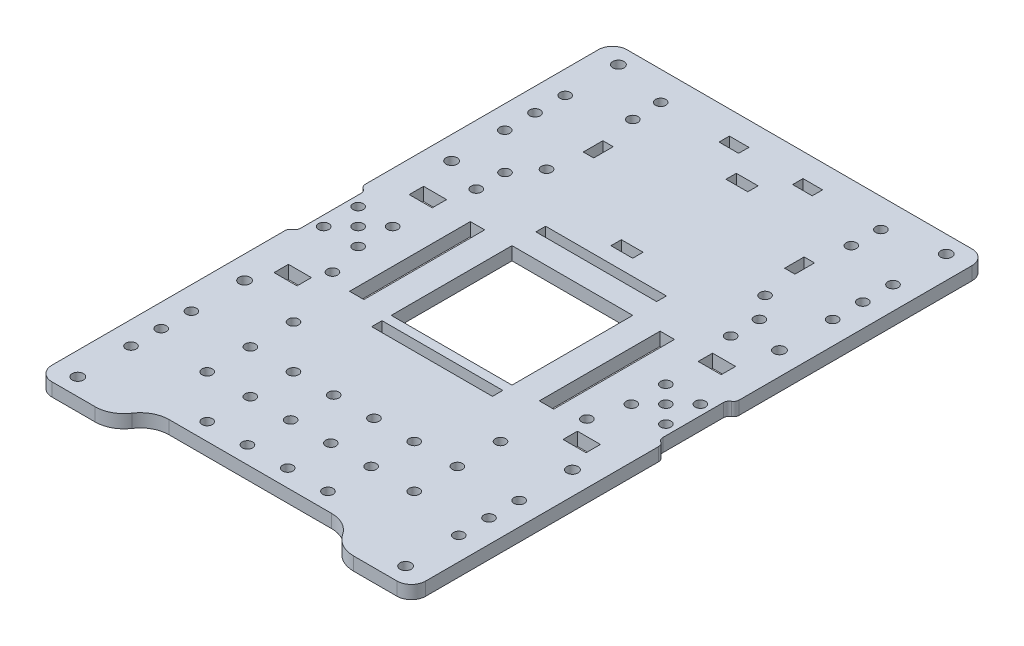
SolidWorks part; units mm, degrees
ref_plane "前视基准面" through (0, 0, 0) normal (0, 0, 1) x (1, 0, 0)
ref_plane "上视基准面" through (0, 0, 0) normal (0, 1, 0) x (1, 0, 0)
ref_plane "右视基准面" through (0, 0, 0) normal (1, 0, 0) x (0, 0, -1)
other "Configuration Table"
sketch "草图2" plane through (0, 0, 0) normal (0, 1, 0) x (1, 0, 0)
  line L0 (-65, 0) -> (65, 0) construction
  line L1 (-65, 100) -> (65, 100)
  line L2 (-65, 100) -> (-65, -100)
  line L3 (-65, -100) -> (65, -100)
  line L4 (65, 100) -> (65, -100)
  line L5 (-65, 100) -> (65, -100) construction
  line L6 (-65, -100) -> (65, 100) construction
  line L7 (65, 0) -> (63, 0) construction
  line L8 (63, 0) -> (59.5, 0) construction
  line L9 (59.5, 0) -> (47.5, 0) construction
  line L10 (47.5, 0) -> (53.5, 0) construction
  line L11 (53.5, 0) -> (53.5, 6) construction
  line L12 (53.5, 6) -> (53.5, -6) construction
  line L13 (53.5, -6) -> (47.5, -6) construction
  line L14 (47.5, -6) -> (47.5, 6) construction
  line L15 (47.5, 6) -> (59.5, 6) construction
  line L16 (59.5, 6) -> (59.5, -6) construction
  line L17 (-65, 0) -> (-63, 0) construction
  line L18 (-63, 0) -> (-59.5, 0) construction
  line L19 (-59.5, 0) -> (-47.5, 0) construction
  line L20 (-47.5, 0) -> (-53.5, 0) construction
  line L21 (-53.5, 0) -> (-53.5, 6) construction
  line L22 (-53.5, 6) -> (-53.5, -6) construction
  line L23 (-53.5, -6) -> (-59.5, -6) construction
  line L24 (-59.5, -6) -> (-59.5, 6) construction
  line L25 (-59.5, 6) -> (-47.5, 6) construction
  line L26 (-47.5, 6) -> (-47.5, -6) construction
  circle A0 centre (-59.5, 6) radius 1.8
  circle A1 centre (-47.5, 6) radius 1.8
  circle A2 centre (-59.5, -6) radius 1.8
  circle A3 centre (-47.5, -6) radius 1.8
  circle A4 centre (-53.5, 0) radius 1.8
  circle A5 centre (53.5, 0) radius 1.8
  circle A6 centre (59.5, 6) radius 1.8
  circle A7 centre (59.5, -6) radius 1.8
  circle A8 centre (47.5, -6) radius 1.8
  circle A9 centre (47.5, 6) radius 1.8
  point P0 (0, 0)
  dimension "D13" = 3.6
  dimension "D14" = 3.6
  dimension "D15" = 3.6
  dimension "D16" = 3.6
  dimension "D17" = 3.6
  dimension "D18" = 3.6
  dimension "D19" = 3.6
  dimension "D20" = 3.6
  dimension "D21" = 3.6
  dimension "D22" = 3.6
  dimension "D1" = 200
  dimension "D2" = 130
  dimension "D3" = 2
  dimension "D4" = 3.5
  dimension "D5" = 12
  dimension "D6" = 6
  dimension "D7" = 12
  dimension "D8" = 2
  dimension "D9" = 3.5
  dimension "D10" = 12
  dimension "D11" = 6
  dimension "D12" = 12
extrude "凸台-拉伸1" add sketch "草图2" along normal blind 4.6
fillet "圆角1" radius 5 4 edges at (-65, 2.3, -100) (65, 2.3, -100) (-65, 2.3, 100) (65, 2.3, 100)
sketch "草图3" plane through (0, 4.6, 0) normal (0, 1, 0) x (1, 0, 0)
  line L0 (-65, 0) -> (65, 0) construction
  line L1 (-65, 95) -> (-65, -95) construction
  line L2 (65, -95) -> (65, 95) construction
  line L4 (-63, 12) -> (-67, 12)
  line L5 (-63, 12) -> (-63, -12)
  line L6 (-63, -12) -> (-67, -12)
  line L7 (-67, 12) -> (-67, -12)
  line L8 (-63, 12) -> (-67, -12) construction
  line L9 (-63, -12) -> (-67, 12) construction
  line L10 (63, 12) -> (67, 12)
  line L11 (63, 12) -> (63, -12)
  line L12 (63, -12) -> (67, -12)
  line L13 (67, 12) -> (67, -12)
  line L14 (63, 12) -> (67, -12) construction
  line L15 (63, -12) -> (67, 12) construction
  dimension "D1" = 24
  dimension "D2" = 4
  dimension "D3" = 24
  dimension "D4" = 4
extrude "切除-拉伸1" cut sketch "草图3" against normal blind 4.6
fillet "圆角2" radius 2 4 edges at (65, 2.3, 12) (65, 2.3, -12) (-65, 2.3, 12) (-65, 2.3, -12)
fillet "圆角3" radius 2 4 edges at (-63, 2.3, 12) (-63, 2.3, -12) (63, 2.3, 12) (63, 2.3, -12)
sketch "草图4" plane through (0, 0, 0) normal (0, 1, 0) x (1, 0, 0)
  line L0 (65, 14) -> (57, 14) construction
  line L1 (57, 14) -> (57, 120) construction
  line L2 (65, -14) -> (57, -14) construction
  line L3 (65, -95) -> (65, -14) construction
  line L4 (57, -14) -> (57, -94) construction
  line L5 (57, -94) -> (57, -65) construction
  line L6 (57, -65) -> (57, -54) construction
  line L7 (-65, -94) -> (-57, -94) construction
  line L8 (-65, -14) -> (-65, -95) construction
  line L9 (-57, -94) -> (-57, -65) construction
  line L10 (-57, -65) -> (-57, -54.5) construction
  line L11 (-57, -54.5) -> (-57, -65) construction
  line L12 (-57, -65) -> (-57, -36) construction
  line L13 (57, -65) -> (57, -36) construction
  line L14 (57, 14) -> (57, 36) construction
  line L15 (57, 36) -> (57, 65) construction
  line L16 (57, 65) -> (57, 75.5) construction
  line L17 (57, 75.5) -> (57, 54.5) construction
  line L18 (57, 65) -> (57, 94) construction
  line L19 (-65, 14) -> (-57, 14) construction
  line L20 (-57, 14) -> (-57, 36) construction
  line L21 (-57, 36) -> (-57, 54.5) construction
  line L22 (-57, 54.5) -> (-57, 65) construction
  line L23 (-57, 65) -> (-57, 75.5) construction
  line L24 (-57, 75.5) -> (-57, 94) construction
  line L25 (-57, -65) -> (-57, -75.5) construction
  line L26 (-57, -75.5) -> (57, -75.5) construction
  line L27 (57, -65) -> (57, -54.5) construction
  arc A0 (65, -14) -> (64, -12.2679) centre (63, -14) ccw construction
  circle A1 centre (57, 65) radius 1.8
  circle A2 centre (57, 75.5) radius 1.8
  circle A3 centre (57, 54.5) radius 1.8
  circle A4 centre (57, 94) radius 1.95
  circle A5 centre (57, 36) radius 1.95
  circle A6 centre (-57, 94) radius 1.95
  circle A7 centre (-57, 75.5) radius 1.8
  circle A8 centre (-57, 65) radius 1.8
  circle A9 centre (-57, 54.5) radius 1.8
  circle A10 centre (-57, 36) radius 1.95
  circle A11 centre (-57, -36) radius 1.95
  circle A12 centre (-57, -65) radius 1.8
  circle A13 centre (-57, -54.5) radius 1.8
  circle A14 centre (-57, -75.5) radius 1.8
  circle A15 centre (-57, -94) radius 1.95
  circle A16 centre (57, -65) radius 1.8
  circle A18 centre (57, -75.5) radius 1.8
  circle A19 centre (57, -54.5) radius 1.8
  circle A20 centre (57, -36) radius 1.95
  circle A21 centre (57, -94) radius 1.95
  dimension "D15" = 3.6
  dimension "D16" = 3.6
  dimension "D17" = 3.6
  dimension "D18" = 3.9
  dimension "D19" = 3.9
  dimension "D20" = 3.9
  dimension "D21" = 3.6
  dimension "D22" = 3.6
  dimension "D23" = 3.6
  dimension "D24" = 3.9
  dimension "D25" = 3.9
  dimension "D26" = 3.6
  dimension "D27" = 3.6
  dimension "D29" = 3.6
  dimension "D30" = 3.9
  dimension "D31" = 3.6
  dimension "D32" = 10.5
  dimension "D33" = 3.6
  dimension "D34" = 3.6
  dimension "D35" = 3.9
  dimension "D36" = 3.9
  dimension "D1" = 8
  dimension "D2" = 106
  dimension "D3" = 8
  dimension "D4" = 80
  dimension "D5" = 29
  dimension "D6" = 11
  dimension "D7" = 8
  dimension "D8" = 29
  dimension "D9" = 22
  dimension "D10" = 29
  dimension "D11" = 10.5
  dimension "D12" = 21
  dimension "D13" = 29
  dimension "D14" = 8
  dimension "D28" = 10.5
extrude "切除-拉伸2" cut sketch "草图4" along normal blind 4.6
sketch "草图5" plane through (0, 4.6, 0) normal (0, 1, 0) x (1, 0, 0)
  line L0 (0, 100) -> (38.3, 100) construction
  line L1 (60, 100) -> (-60, 100) construction
  line L2 (38.3, 100) -> (-38.3, 100) construction
  line L3 (-38.3, 100) -> (-38.3, 90) construction
  line L4 (-38.3, 90) -> (-12.8, 90) construction
  line L5 (38.3, 100) -> (38.3, 90) construction
  line L6 (38.3, 90) -> (12.8, 90) construction
  line L7 (0, 21) -> (0, 31) construction
  line L8 (-16.2, 91.8) -> (-9.4, 91.8)
  line L9 (-16.2, 91.8) -> (-16.2, 88.2)
  line L10 (-16.2, 88.2) -> (-9.4, 88.2)
  line L11 (-9.4, 91.8) -> (-9.4, 88.2)
  line L12 (-16.2, 91.8) -> (-9.4, 88.2) construction
  line L13 (-16.2, 88.2) -> (-9.4, 91.8) construction
  line L14 (9.4, 91.8) -> (16.2, 91.8)
  line L15 (9.4, 91.8) -> (9.4, 88.2)
  line L16 (9.4, 88.2) -> (16.2, 88.2)
  line L17 (16.2, 91.8) -> (16.2, 88.2)
  line L18 (9.4, 91.8) -> (16.2, 88.2) construction
  line L19 (9.4, 88.2) -> (16.2, 91.8) construction
  line L20 (-21, 21) -> (21, 21)
  line L21 (-21, 21) -> (-21, -21)
  line L22 (-21, -21) -> (21, -21)
  line L23 (21, 21) -> (21, -21)
  line L24 (-21, 21) -> (21, -21) construction
  line L25 (-21, -21) -> (21, 21) construction
  line L26 (0, 31) -> (0, -21) construction
  line L27 (0, -21) -> (0, -31) construction
  line L28 (-60, -100) -> (60, -100) construction
  line L29 (-21, 32.7) -> (21, 32.7)
  line L30 (-21, 32.7) -> (-21, 29.3)
  line L31 (-21, 29.3) -> (21, 29.3)
  line L32 (21, 32.7) -> (21, 29.3)
  line L33 (-21, 32.7) -> (21, 29.3) construction
  line L34 (-21, 29.3) -> (21, 32.7) construction
  line L35 (-21, -29.3) -> (21, -29.3)
  line L36 (-21, -29.3) -> (-21, -32.7)
  line L37 (-21, -32.7) -> (21, -32.7)
  line L38 (21, -29.3) -> (21, -32.7)
  line L39 (-21, -29.3) -> (21, -32.7) construction
  line L40 (-21, -32.7) -> (21, -29.3) construction
  line L41 (-35, -91) -> (35, -91)
  line L42 (-35, -91) -> (-35, -109)
  line L43 (-35, -109) -> (35, -109)
  line L44 (35, -91) -> (35, -109)
  line L45 (-35, -91) -> (35, -109) construction
  line L46 (-35, -109) -> (35, -91) construction
  circle A0 centre (38.3, 90) radius 1.8
  circle A1 centre (-38.3, 90) radius 1.8
  point P19 (0, 0)
  point P37 (0, -100)
  dimension "D7" = 3.6
  dimension "D8" = 3.6
  dimension "D1" = 38.3
  dimension "D2" = 76.6
  dimension "D3" = 10
  dimension "D4" = 25.5
  dimension "D5" = 10
  dimension "D6" = 25.5
  dimension "D9" = 3.6
  dimension "D10" = 6.8
  dimension "D11" = 3.6
  dimension "D12" = 6.8
  dimension "D13" = 42
  dimension "D14" = 10
  dimension "D15" = 10
  dimension "D16" = 3.4
  dimension "D17" = 42
  dimension "D18" = 3.4
  dimension "D19" = 42
  dimension "D20" = 18
  dimension "D21" = 70
extrude "切除-拉伸3" cut sketch "草图5" against normal blind 4.6
fillet "圆角4" radius 10 2 edges at (-35, 2.3, 100) (35, 2.3, 100)
fillet "圆角5" radius 10 2 edges at (-35, 2.3, 91) (35, 2.3, 91)
sketch "草图6" plane through (0, 4.6, 0) normal (0, 1, 0) x (1, 0, 0)
  line L0 (0, -91) -> (0, -85) construction
  line L1 (28.2466, -91) -> (-28.2466, -91) construction
  line L2 (0, -85) -> (-7, -85) construction
  line L3 (-7, -85) -> (7, -85) construction
  line L4 (7, -85) -> (21, -85) construction
  line L5 (21, -85) -> (21, -70) construction
  line L6 (21, -70) -> (21, -55) construction
  line L7 (21, -55) -> (7, -55) construction
  line L8 (7, -55) -> (-7, -55) construction
  line L9 (-7, -55) -> (-21, -55) construction
  line L10 (-21, -55) -> (-35, -55) construction
  line L11 (-35, -55) -> (-35, -70) construction
  line L12 (-35, -70) -> (-35, -85) construction
  line L13 (-35, -85) -> (-21, -85) construction
  line L14 (21, -85) -> (35, -85) construction
  line L15 (35, -85) -> (35, -70) construction
  line L16 (35, -70) -> (35, -55) construction
  line L17 (35, -55) -> (35, -40) construction
  line L18 (35, -40) -> (21, -40) construction
  line L19 (21, -40) -> (7, -40) construction
  line L20 (7, -40) -> (-7, -40) construction
  line L21 (-7, -40) -> (-21, -40) construction
  line L22 (-21, -40) -> (-35, -40) construction
  line L23 (-35, -40) -> (-35, -70) construction
  line L24 (-35, -70) -> (-21, -70) construction
  line L25 (-21, -70) -> (-7, -70) construction
  line L26 (-7, -70) -> (7, -70) construction
  line L27 (21, -70) -> (36, -70) construction
  line L28 (36, -70) -> (36, -55) construction
  line L29 (36, -55) -> (36, -40) construction
  line L30 (-21, -70) -> (-36, -70) construction
  line L31 (-36, -70) -> (-36, -55) construction
  line L32 (-36, -55) -> (-36, -40) construction
  circle A0 centre (-7, -85) radius 1.8
  circle A1 centre (-21, -85) radius 1.8
  circle A2 centre (7, -85) radius 1.8
  circle A3 centre (21, -85) radius 1.8
  circle A4 centre (21, -70) radius 1.8
  circle A5 centre (7, -70) radius 1.8
  circle A6 centre (-7, -70) radius 1.8
  circle A7 centre (-21, -70) radius 1.8
  circle A8 centre (-21, -55) radius 1.8
  circle A9 centre (-7, -55) radius 1.8
  circle A10 centre (7, -55) radius 1.8
  circle A11 centre (21, -55) radius 1.8
  circle A12 centre (36, -70) radius 1.8
  circle A13 centre (36, -55) radius 1.8
  circle A14 centre (36, -40) radius 1.8
  circle A15 centre (-36, -40) radius 1.8
  circle A16 centre (-36, -55) radius 1.8
  circle A17 centre (-36, -70) radius 1.8
  dimension "D15" = 3.6
  dimension "D16" = 3.6
  dimension "D17" = 3.6
  dimension "D18" = 3.6
  dimension "D19" = 3.6
  dimension "D20" = 3.6
  dimension "D21" = 3.6
  dimension "D22" = 3.6
  dimension "D23" = 3.6
  dimension "D24" = 3.6
  dimension "D25" = 3.6
  dimension "D26" = 3.6
  dimension "D27" = 15
  dimension "D33" = 3.6
  dimension "D34" = 3.6
  dimension "D35" = 3.6
  dimension "D36" = 3.6
  dimension "D37" = 3.6
  dimension "D38" = 3.6
  dimension "D1" = 6
  dimension "D2" = 7
  dimension "D3" = 14
  dimension "D4" = 14
  dimension "D5" = 15
  dimension "D6" = 15
  dimension "D7" = 14
  dimension "D8" = 14
  dimension "D9" = 14
  dimension "D10" = 14
  dimension "D11" = 15
  dimension "D12" = 14
  dimension "D13" = 14
  dimension "D14" = 15
  dimension "D28" = 15
  dimension "D29" = 15
  dimension "D30" = 15
  dimension "D31" = 15
  dimension "D32" = 15
extrude "切除-拉伸4" cut sketch "草图6" against normal blind 4.6
sketch "草图7" plane through (0, 4.6, 0) normal (0, 1, 0) x (1, 0, 0)
  line L0 (0, 100) -> (38, 100) construction
  line L1 (60, 100) -> (-60, 100) construction
  line L2 (38, 100) -> (-38, 100) construction
  line L3 (-38, 100) -> (-38, 80) construction
  line L4 (-38, 80) -> (-38, 50) construction
  line L5 (-38, 50) -> (38, 50) construction
  line L6 (38, 50) -> (38, 80) construction
  circle A0 centre (-38, 80) radius 1.8
  circle A1 centre (38, 80) radius 1.8
  circle A2 centre (38, 50) radius 1.8
  circle A3 centre (-38, 50) radius 1.8
  dimension "D7" = 3.6
  dimension "D8" = 3.6
  dimension "D9" = 3.6
  dimension "D10" = 3.6
  dimension "D1" = 38
  dimension "D2" = 76
  dimension "D3" = 20
  dimension "D4" = 30
  dimension "D5" = 76
  dimension "D6" = 30
extrude "切除-拉伸5" cut sketch "草图7" against normal blind 4.6
sketch "草图8" plane through (0, 4.6, 0) normal (0, 1, 0) x (1, 0, 0)
  line L0 (-38, 80) -> (38, 50) construction
  line L1 (38, 50) -> (0, 65) construction
  line L2 (0, 65) -> (-35, 65) construction
  line L3 (-35, 65) -> (35, 65) construction
  line L4 (35, 65) -> (0, 65) construction
  line L5 (0, 65) -> (0, 80) construction
  line L6 (0, 80) -> (0, 40) construction
  line L8 (-3.7805, 81.7985) -> (3.7805, 81.7985)
  line L9 (-3.7805, 81.7985) -> (-3.7805, 78.2015)
  line L10 (-3.7805, 78.2015) -> (3.7805, 78.2015)
  line L11 (3.7805, 81.7985) -> (3.7805, 78.2015)
  line L12 (-3.7805, 81.7985) -> (3.7805, 78.2015) construction
  line L13 (-3.7805, 78.2015) -> (3.7805, 81.7985) construction
  line L14 (-3.7805, 38.1892) -> (3.7805, 38.1892)
  line L15 (-3.7805, 38.1892) -> (-3.7805, 41.8108)
  line L16 (-3.7805, 41.8108) -> (3.7805, 41.8108)
  line L17 (3.7805, 38.1892) -> (3.7805, 41.8108)
  line L18 (-3.7805, 38.1892) -> (3.7805, 41.8108) construction
  line L19 (-3.7805, 41.8108) -> (3.7805, 38.1892) construction
  line L20 (33.2, 68.4) -> (36.8, 68.4)
  line L21 (33.2, 68.4) -> (33.2, 61.6)
  line L22 (33.2, 61.6) -> (36.8, 61.6)
  line L23 (36.8, 68.4) -> (36.8, 61.6)
  line L24 (33.2, 68.4) -> (36.8, 61.6) construction
  line L25 (33.2, 61.6) -> (36.8, 68.4) construction
  line L26 (-36.8, 68.4) -> (-33.2, 68.4)
  line L27 (-36.8, 68.4) -> (-36.8, 61.6)
  line L28 (-36.8, 61.6) -> (-33.2, 61.6)
  line L29 (-33.2, 68.4) -> (-33.2, 61.6)
  line L30 (-36.8, 68.4) -> (-33.2, 61.6) construction
  line L31 (-36.8, 61.6) -> (-33.2, 68.4) construction
  dimension "D1" = 35
  dimension "D2" = 70
  dimension "D3" = 40
  dimension "D4" = 6.8
  dimension "D5" = 3.6
  dimension "D6" = 6.8
  dimension "D7" = 3.6
extrude "切除-拉伸6" cut sketch "草图8" against normal blind 4.6
sketch "草图10" plane through (0, 4.6, 0) normal (0, 1, 0) x (1, 0, 0)
  line L0 (0, 0) -> (44.25, 0) construction
  line L1 (44.25, 0) -> (-44.25, 0) construction
  line L2 (36, -38.2) -> (73.5514, -38.2) construction
  line L3 (73.5514, -38.2) -> (-76.1567, -38.2) construction
  line L4 (44.25, 0) -> (44.25, -38.2) construction
  line L5 (44.25, -38.2) -> (44.25, -18.2) construction
  line L6 (-44.25, 0) -> (-44.25, -38.2) construction
  line L7 (-44.25, -38.2) -> (-44.25, -18.1899) construction
  line L8 (-44.25, -18.1899) -> (-43.1477, 41.8) construction
  line L9 (-43.1477, 41.8) -> (44.25, 41.8) construction
  line L10 (0, 38.1892) -> (-44.25, 38.1892) construction
  line L11 (-3.7805, 38.1892) -> (3.7805, 38.1892) construction
  line L12 (-44.25, 38.1892) -> (44.25, 38.1892) construction
  line L13 (-44.25, -18.1899) -> (-44.25, 41.8101) construction
  line L14 (44.25, -18.2) -> (44.25, 41.8) construction
  line L15 (44.25, -18.2) -> (44.25, -8.2) construction
  line L16 (-44.25, -18.1899) -> (-44.25, -8.1899) construction
  line L17 (-44.25, -18.1899) -> (-44.25, 31.8101) construction
  line L18 (-44.25, 31.8101) -> (44.25, 31.8101) construction
  circle A0 centre (36, -40) radius 1.8 construction
  circle A1 centre (44.25, 41.8) radius 1.8
  circle A2 centre (-44.25, 41.8101) radius 1.8
  circle A3 centre (-44.25, -18.1899) radius 1.8
  circle A4 centre (44.25, -18.2) radius 1.8
  circle A5 centre (-44.25, 31.8101) radius 1.8
  circle A6 centre (44.25, 31.8101) radius 1.8
  dimension "D9" = 3.6
  dimension "D10" = 3.6
  dimension "D11" = 3.6
  dimension "D12" = 3.6
  dimension "D16" = 3.6
  dimension "D17" = 3.6
  dimension "D1" = 44.25
  dimension "D2" = 88.5
  dimension "D3" = 20
  dimension "D4" = 60
  dimension "D5" = 44.25
  dimension "D6" = 88.5
  dimension "D7" = 60
  dimension "D8" = 60
  dimension "D13" = 10
  dimension "D14" = 10
  dimension "D15" = 50
extrude "切除-拉伸8" cut sketch "草图10" against normal blind 4.6
sketch "草图9" plane through (0, 4.6, 0) normal (0, 1, 0) x (1, 0, 0)
  line L0 (21, 0) -> (33, 0) construction
  line L1 (21, -21) -> (21, 21) construction
  line L2 (-21, 0) -> (-33, 0) construction
  line L3 (-21, 21) -> (-21, -21) construction
  line L4 (35.5, -21) -> (65, -21) construction
  line L9 (30.5, 21) -> (35.5, -21) construction
  line L10 (30.5, -21) -> (35.5, 21) construction
  line L15 (-35.5, 21) -> (-30.5, -21) construction
  line L16 (-35.5, -21) -> (-30.5, 21) construction
  line L17 (65, -95) -> (65, -14) construction
  line L18 (-35.5, -21) -> (-65, -21) construction
  line L23 (46.25, -18.5) -> (54.25, -23.5) construction
  line L24 (46.25, -23.5) -> (54.25, -18.5) construction
  line L25 (-65, -14) -> (-65, -95) construction
  line L26 (-35.5, 21) -> (-65, 21) construction
  line L31 (-54.25, -18.5) -> (-46.25, -23.5) construction
  line L32 (-54.25, -23.5) -> (-46.25, -18.5) construction
  line L33 (-65, 95) -> (-65, 14) construction
  line L34 (35.5, 21) -> (65, 21) construction
  line L35 (-54.25, 23.5) -> (-46.25, 23.5)
  line L36 (-54.25, 23.5) -> (-54.25, 18.5)
  line L37 (-54.25, 18.5) -> (-46.25, 18.5)
  line L38 (-46.25, 23.5) -> (-46.25, 18.5)
  line L39 (-54.25, 23.5) -> (-46.25, 18.5) construction
  line L40 (-54.25, 18.5) -> (-46.25, 23.5) construction
  line L41 (65, 14) -> (65, 95) construction
  line L42 (50.25, -21) -> (50.25, -31) construction
  line L43 (46.25, 23.5) -> (54.25, 23.5)
  line L44 (46.25, 23.5) -> (46.25, 18.5)
  line L45 (46.25, 18.5) -> (54.25, 18.5)
  line L46 (54.25, 23.5) -> (54.25, 18.5)
  line L47 (46.25, 23.5) -> (54.25, 18.5) construction
  line L48 (46.25, 18.5) -> (54.25, 23.5) construction
  line L49 (50.25, -31) -> (50.25, -26) construction
  line L50 (50.25, -26) -> (-50.25, -26) construction
  line L52 (-54.25, -23.5) -> (-46.25, -23.5)
  line L53 (-54.25, -23.5) -> (-54.25, -28.5)
  line L54 (-54.25, -28.5) -> (-46.25, -28.5)
  line L55 (-46.25, -23.5) -> (-46.25, -28.5)
  line L56 (-54.25, -23.5) -> (-46.25, -28.5) construction
  line L57 (-54.25, -28.5) -> (-46.25, -23.5) construction
  line L58 (46.25, -23.5) -> (54.25, -23.5)
  line L59 (46.25, -23.5) -> (46.25, -28.5)
  line L60 (46.25, -28.5) -> (54.25, -28.5)
  line L61 (54.25, -23.5) -> (54.25, -28.5)
  line L62 (46.25, -23.5) -> (54.25, -28.5) construction
  line L63 (46.25, -28.5) -> (54.25, -23.5) construction
  line L64 (30.5, 21) -> (35.5, 21)
  line L65 (30.5, 21) -> (30.5, -21)
  line L66 (30.5, -21) -> (35.5, -21)
  line L67 (35.5, 21) -> (35.5, -21)
  line L68 (30.5, 21) -> (35.5, -21) construction
  line L69 (30.5, -21) -> (35.5, 21) construction
  line L70 (-35.5, 21) -> (-30.5, 21)
  line L71 (-35.5, 21) -> (-35.5, -21)
  line L72 (-35.5, -21) -> (-30.5, -21)
  line L73 (-30.5, 21) -> (-30.5, -21)
  line L74 (-35.5, 21) -> (-30.5, -21) construction
  line L75 (-35.5, -21) -> (-30.5, 21) construction
  point P17 (50.25, -21)
  point P25 (-50.25, -21)
  point P33 (-50.25, 21)
  point P41 (50.25, 21)
  dimension "D1" = 12
  dimension "D2" = 12
  dimension "D3" = 42
  dimension "D4" = 5
  dimension "D5" = 42
  dimension "D6" = 5
  dimension "D7" = 5
  dimension "D8" = 8
  dimension "D9" = 5
  dimension "D10" = 8
  dimension "D11" = 5
  dimension "D12" = 8
  dimension "D13" = 5
  dimension "D14" = 8
  dimension "D15" = 10
  dimension "D16" = 5
  dimension "D17" = 8
  dimension "D18" = 5
  dimension "D19" = 8
extrude "切除-拉伸9" cut sketch "草图9" against normal blind 4.6
sketch "草图12" plane through (0, 0, 0) normal (0, -1, 0) x (1, 0, 0)
  line L0 (-46.25, 28.5) -> (-46.25, 23.5) construction
  line L1 (-65, 100) -> (-46.25, 100)
  line L2 (-65, 100) -> (-65, 28.5)
  line L3 (-65, 28.5) -> (-46.25, 28.5)
  line L4 (-46.25, 100) -> (-46.25, 28.5)
  line L5 (-54.25, 28.5) -> (-46.25, 28.5) construction
  line L6 (65, 95) -> (65, 100.0021) construction
  line L7 (-60, -100) -> (-65, -100) construction
  line L8 (65, 100.0021) -> (46.25, 100.0021)
  line L9 (65, 100.0021) -> (65, 28.5)
  line L10 (65, 28.5) -> (46.25, 28.5)
  line L11 (46.25, 100.0021) -> (46.25, 28.5)
  line L12 (-46.25, -23.5) -> (-54.25, -23.5) construction
  line L13 (-65, -100) -> (-50.25, -100)
  line L14 (-65, -100) -> (-65, -23.5)
  line L15 (-65, -23.5) -> (-50.25, -23.5)
  line L16 (-50.25, -100) -> (-50.25, -23.5)
  line L17 (54.25, -23.5) -> (46.25, -23.5) construction
  line L18 (65, -99.9979) -> (50.25, -99.9979)
  line L19 (65, -99.9979) -> (65, -23.5)
  line L20 (65, -23.5) -> (50.25, -23.5)
  line L21 (50.25, -99.9979) -> (50.25, -23.5)
  line L22 (-50.25, -55.9334) -> (50.25, -55.9334) construction
  line L23 (50.25, -55.9334) -> (50.25, -72.845) construction
  line L24 (50.25, -72.845) -> (-50.25, -72.845) construction
  line L25 (-21, 85) -> (-21, 70) construction
  line L26 (-21, 70) -> (-21, 77.5) construction
  line L27 (-21, 77.5) -> (-46.25, 77.5) construction
  line L28 (-46.25, 77.5) -> (46.25, 77.5) construction
  line L29 (46.25, 77.5) -> (0, 77.5) construction
  line L30 (0, 77.5) -> (0, 62.5) construction
  line L31 (0, 62.5) -> (0, 47.5) construction
  line L32 (0, 77.5) -> (0, 92.5) construction
  line L33 (-28.2466, 91) -> (-46.25, 91) construction
  line L34 (-46.25, 91) -> (46.25, 91) construction
  line L35 (-21, 32.7) -> (-46.25, 32.7) construction
  line L36 (-46.25, 79.5003) -> (46.25, 79.5003)
  line L37 (-46.25, 79.5003) -> (-46.25, 75.4997)
  line L38 (-46.25, 75.4997) -> (46.25, 75.4997)
  line L39 (46.25, 79.5003) -> (46.25, 75.4997)
  line L40 (-46.25, 79.5003) -> (46.25, 75.4997) construction
  line L41 (-46.25, 75.4997) -> (46.25, 79.5003) construction
  line L42 (-46.25, 64.5) -> (46.25, 64.5)
  line L43 (-46.25, 64.5) -> (-46.25, 60.5)
  line L44 (-46.25, 60.5) -> (46.25, 60.5)
  line L45 (46.25, 64.5) -> (46.25, 60.5)
  line L46 (-46.25, 64.5) -> (46.25, 60.5) construction
  line L47 (-46.25, 60.5) -> (46.25, 64.5) construction
  line L48 (-46.25, 49.5) -> (46.25, 49.5)
  line L49 (-46.25, 49.5) -> (-46.25, 45.5)
  line L50 (-46.25, 45.5) -> (46.25, 45.5)
  line L51 (46.25, 49.5) -> (46.25, 45.5)
  line L52 (-46.25, 49.5) -> (46.25, 45.5) construction
  line L53 (-46.25, 45.5) -> (46.25, 49.5) construction
  line L54 (-46.25, 91) -> (46.25, 91)
  line L55 (-46.25, 91) -> (-46.25, 89)
  line L56 (-46.25, 89) -> (46.25, 89)
  line L57 (46.25, 91) -> (46.25, 89)
  line L58 (-46.25, 32.7) -> (46.25, 32.7) construction
  line L59 (0, -55.9334) -> (0, -57.8166) construction
  line L60 (-46.25, 32.7) -> (46.25, 32.7)
  line L61 (-46.25, 32.7) -> (-46.25, 34.7)
  line L62 (-46.25, 34.7) -> (46.25, 34.7)
  line L63 (46.25, 32.7) -> (46.25, 34.7)
  line L64 (-38, -81.8) -> (-38, -88.2252) construction
  line L65 (-50.25, -54.875) -> (50.25, -54.875)
  line L66 (-50.25, -54.875) -> (-50.25, -58.875)
  line L67 (-50.25, -58.875) -> (50.25, -58.875)
  line L68 (50.25, -54.875) -> (50.25, -58.875)
  line L69 (-50.25, -54.875) -> (50.25, -58.875) construction
  line L70 (-50.25, -58.875) -> (50.25, -54.875) construction
  line L71 (-50.25, -74.845) -> (50.25, -74.845)
  line L72 (-50.25, -74.845) -> (-50.25, -70.845)
  line L73 (-50.25, -70.845) -> (50.25, -70.845)
  line L74 (50.25, -74.845) -> (50.25, -70.845)
  line L75 (-50.25, -74.845) -> (50.25, -70.845) construction
  line L76 (-50.25, -70.845) -> (50.25, -74.845) construction
  line L77 (-38, -85.0126) -> (67.8048, -85.0126) construction
  line L78 (0, -81.7985) -> (0, -85.0126) construction
  line L79 (3.7805, -81.7985) -> (-3.7805, -81.7985) construction
  line L80 (0, -85.0126) -> (0, -95.8032) construction
  line L81 (-50.25, -84.0126) -> (50.25, -84.0126)
  line L82 (-50.25, -84.0126) -> (-50.25, -86.0126)
  line L83 (-50.25, -86.0126) -> (50.25, -86.0126)
  line L84 (50.25, -84.0126) -> (50.25, -86.0126)
  line L85 (-50.25, -84.0126) -> (50.25, -86.0126) construction
  line L86 (-50.25, -86.0126) -> (50.25, -84.0126) construction
  line L87 (0, -56.875) -> (0, -72.845) construction
  line L88 (-50.25, -94.3032) -> (50.25, -94.3032)
  line L89 (-50.25, -94.3032) -> (-50.25, -97.3032)
  line L90 (-50.25, -97.3032) -> (50.25, -97.3032)
  line L91 (50.25, -94.3032) -> (50.25, -97.3032)
  line L92 (-50.25, -94.3032) -> (50.25, -97.3032) construction
  line L93 (-50.25, -97.3032) -> (50.25, -94.3032) construction
  line L94 (3.7805, -80) -> (36.2, -80) construction
  line L95 (-2, -58.875) -> (2, -58.875)
  line L96 (-2, -58.875) -> (-2, -70.845)
  line L97 (-2, -70.845) -> (2, -70.845)
  line L98 (2, -58.875) -> (2, -70.845)
  line L99 (-2, -58.875) -> (2, -70.845) construction
  line L100 (-2, -70.845) -> (2, -58.875) construction
  line L101 (3.7805, -78.2015) -> (3.7805, -81.7985) construction
  line L102 (-3.7805, -80) -> (-36.2, -80) construction
  line L103 (-3.7805, -81.7985) -> (-3.7805, -78.2015) construction
  line L104 (22.8, 55) -> (34.2, 55) construction
  line L105 (17.9902, -85.155) -> (21.9902, -85.155)
  line L106 (17.9902, -85.155) -> (17.9902, -74.845)
  line L107 (17.9902, -74.845) -> (21.9902, -74.845)
  line L108 (21.9902, -85.155) -> (21.9902, -74.845)
  line L109 (17.9902, -85.155) -> (21.9902, -74.845) construction
  line L110 (17.9902, -74.845) -> (21.9902, -85.155) construction
  line L111 (-21.9902, -85.845) -> (-17.9902, -85.845)
  line L112 (-21.9902, -85.845) -> (-21.9902, -74.155)
  line L113 (-21.9902, -74.155) -> (-17.9902, -74.155)
  line L114 (-17.9902, -85.845) -> (-17.9902, -74.155)
  line L115 (-21.9902, -85.845) -> (-17.9902, -74.155) construction
  line L116 (-21.9902, -74.155) -> (-17.9902, -85.845) construction
  line L117 (-2, -84.9529) -> (2, -84.9529)
  line L118 (-2, -84.9529) -> (-2, -95.8629)
  line L119 (-2, -95.8629) -> (2, -95.8629)
  line L120 (2, -84.9529) -> (2, -95.8629)
  line L121 (-2, -84.9529) -> (2, -95.8629) construction
  line L122 (-2, -95.8629) -> (2, -84.9529) construction
  line L123 (-2, 49) -> (2, 49)
  line L124 (-2, 49) -> (-2, 91)
  line L125 (-2, 91) -> (2, 91)
  line L126 (2, 49) -> (2, 91)
  line L127 (-2, 49) -> (2, 91) construction
  line L128 (-2, 91) -> (2, 49) construction
  line L129 (-34.2, 55) -> (-22.8, 55) construction
  line L131 (26.5, 75.3) -> (30.5, 75.3)
  line L132 (26.5, 75.3) -> (26.5, 34.7)
  line L133 (26.5, 34.7) -> (30.5, 34.7)
  line L134 (30.5, 75.3) -> (30.5, 34.7)
  line L135 (26.5, 75.3) -> (30.5, 34.7) construction
  line L136 (26.5, 34.7) -> (30.5, 75.3) construction
  line L137 (-30.5, 75.3) -> (-26.5, 75.3)
  line L138 (-30.5, 75.3) -> (-30.5, 34.7)
  line L139 (-30.5, 34.7) -> (-26.5, 34.7)
  line L140 (-26.5, 75.3) -> (-26.5, 34.7)
  line L141 (-30.5, 75.3) -> (-26.5, 34.7) construction
  line L142 (-30.5, 34.7) -> (-26.5, 75.3) construction
  circle A0 centre (-57, 94) radius 1.95
  circle A1 centre (-57, 75.5) radius 1.8
  circle A2 centre (-57, 65) radius 1.8143
  circle A3 centre (-57, 54.5) radius 1.8
  circle A4 centre (-57, 36) radius 1.95
  circle A5 centre (57, 94) radius 1.95
  circle A6 centre (57, 75.5) radius 1.8
  circle A7 centre (57, 65) radius 1.8
  circle A8 centre (57, 54.5) radius 1.8
  circle A9 centre (57, 36) radius 1.95
  circle A10 centre (57, -36) radius 1.95
  circle A11 centre (57, -54.5) radius 1.8
  circle A12 centre (57, -65) radius 1.8
  circle A13 centre (57, -75.5) radius 1.8
  circle A14 centre (57, -94) radius 1.95
  circle A15 centre (-57, -94) radius 1.95
  circle A16 centre (-57, -75.5) radius 1.8
  circle A17 centre (-57, -65) radius 1.8
  circle A18 centre (-57, -54.5) radius 1.8
  circle A19 centre (-57, -36) radius 1.95
  circle A20 centre (-38, -80) radius 1.8 construction
  circle A21 centre (-38.3, -90) radius 1.8 construction
  circle A22 centre (38, -80) radius 1.8 construction
  circle A23 centre (21, 55) radius 1.8 construction
  circle A24 centre (36, 55) radius 1.8 construction
  circle A25 centre (-36, 55) radius 1.8 construction
  circle A26 centre (-21, 55) radius 1.8 construction
  point P133 (0, -56.875)
  point P138 (0, -72.845)
  point P167 (0, -64.86)
  point P183 (19.9902, -80)
  point P188 (-19.9902, -80)
  point P193 (0, -90.4079)
  point P198 (0, 70)
  point P217 (28.5, 55)
  point P222 (-28.5, 55)
  dimension "D1" = 15
  dimension "D2" = 15
  dimension "D3" = 15
  dimension "D4" = 4.0007
  dimension "D5" = 92.5
  dimension "D6" = 4
  dimension "D7" = 4
  dimension "D8" = 2
  dimension "D9" = 2
  dimension "D10" = 4
  dimension "D11" = 4
  dimension "D12" = 2
  dimension "D13" = 3
  dimension "D14" = 11.97
  dimension "D15" = 4
  dimension "D16" = 10.31
  dimension "D17" = 4
  dimension "D18" = 11.69
  dimension "D19" = 4
  dimension "D20" = 10.91
  dimension "D21" = 4
  dimension "D22" = 42
  dimension "D23" = 4
  dimension "D24" = 40.6
  dimension "D25" = 4
  dimension "D26" = 40.6
  dimension "D27" = 4
extrude "凸台-拉伸2" add sketch "草图12" along normal blind 2 contours L4 L1 L2 L3 A4 A3 A2 A1 A0 | L56 L126 L54 L124 | L126 L56 L11 L54 | L56 L124 L54 L4 | L36 L126 L56 L124 | L8 L11 L10 L9 A9 A8 A7 A6 A5 | L126 L38 L11 L36 | L38 L126 L36 L124 | L38 L124 L36 L4 | L42 L126 L38 L124 | L134 L131 L132 L42 | L140 L137 L138 L42 | L138 L42 L4 L44 | L140 L42 L138 L44 | L42 L140 L44 L124 | L44 L126 L42 L124 | L132 L42 L126 L44 | L134 L42 L132 L44 | L42 L134 L44 L11 | L134 L44 L132 L48 | L48 L134 L50 L11 | L134 L50 L132 L62 | L62 L4 L60 L11 | L134 L48 L132 L50 | L48 L140 L50 L132 L126 L123 L124 | L48 L126 L44 L124 | L123 L126 L48 L124 | L140 L44 L138 L48 | L138 L48 L4 L50 | L140 L48 L138 L50 | L140 L50 L138 L62 | L21 L18 L19 L20 A14 A13 A12 A11 A10 | L13 L16 L15 L14 A19 A18 A17 A16 A15 | L16 L67 L21 L65 | L98 L67 L96 L73 | L114 L71 L21 L73 L16 L112 L113 | L81 L108 L71 L106 | L81 L114 L71 L112 | L71 L114 L113 L112 | L117 L120 L83 L21 L81 L108 L105 L106 L114 L111 L112 L16 L118 | L111 L114 L81 L112 | L105 L108 L81 L106 | L120 L117 L118 L83 | L120 L83 L118 L88 | L88 L120 L119 L118 L16 L90 L21 | L120 L88 L118 L119 region at (-55.625, 0, 99.2608) region at (-24.125, 0, 90) region at (0, 0, 90) region at (0, 0, 33.7) region at (-24.125, 0, 77.5) region at (0, 0, 84.2502) region at (24.125, 0, 90) region at (46.9892, 0, 33.7) region at (0, 0, 77.5) region at (-38.375, 0, 47.5) region at (-28.5, 0, 40.1) region at (-38.375, 0, 62.5) region at (0, 0, 69.9998) region at (24.125, 0, 77.5) region at (-28.5, 0, 47.5) region at (38.375, 0, 47.5) region at (28.5, 0, 40.1) region at (-28.5, 0, 69.9) region at (-28.5, 0, 62.5) region at (-14.25, 0, 62.5) region at (0, 0, 62.5) region at (-28.5, 0, 55) region at (0, 0, 47.4833) region at (28.5, 0, 47.5) region at (14.25, 0, 62.5) region at (0, 0, 55) region at (38.375, 0, 62.5) region at (28.5, 0, 55) region at (28.5, 0, 69.9) region at (28.5, 0, 62.5) region at (0, 0, 49.25) region at (-57.6567, 0, -61.5853) region at (-49.2446, 0, -95.8032) region at (57.6567, 0, -61.5842) region at (0, 0, -56.875) region at (-49.2448, 0, -85.0126) region at (0, 0, -90.1579) region at (0, 0, -95.083) region at (0, 0, -85.4827) region at (0.1382, 0, -72.8336) region at (0, 0, -64.86) region at (-19.9902, 0, -79.4288) region at (-19.9902, 0, -84.9288) region at (-19.9902, 0, -74.5) region at (19.9902, 0, -84.5838) region at (19.9902, 0, -79.4288)
sketch "草图13" plane through (0, 0, 0) normal (0, -1, 0) x (1, 0, 0)
  line L0 (0, -41.8108) -> (0, -45.8108) construction
  line L1 (3.7805, -41.8108) -> (-3.7805, -41.8108) construction
  line L3 (-15, -45.8108) -> (15, -45.8108)
  line L4 (-15, -45.8108) -> (-15, -41.8108)
  line L5 (-15, -41.8108) -> (15, -41.8108)
  line L6 (15, -45.8108) -> (15, -41.8108)
  line L7 (-15, -45.8108) -> (15, -41.8108) construction
  line L8 (-15, -41.8108) -> (15, -45.8108) construction
  point P5 (0, -43.8108)
  dimension "D1" = 4
  dimension "D2" = 4
  dimension "D3" = 30
extrude "凸台-拉伸3" add sketch "草图13" along normal blind 2
fillet "圆角6" radius 5 4 edges at (-65, -1, 100) (65, -1, 100.0021) (-65, -1, -100) (65, -1, -99.9979)
sketch "草图14" plane through (0, 4.6, 0) normal (0, 1, 0) x (1, 0, 0)
  line L1 (21, -32.7) -> (-21, -32.7)
  line L2 (21, -32.7) -> (21, -29.3)
  line L3 (21, -29.3) -> (-21, -29.3)
  line L4 (-21, -32.7) -> (-21, -29.3)
extrude "凸台-拉伸4" add sketch "草图14" against normal up to surface (4.6 mm away) up to face at (0, 0, 1.9679)
sketch "草图15" plane through (0, 4.6, 0) normal (0, 1, 0) x (1, 0, 0)
  line L0 (0, -21) -> (0, -26) construction
  line L1 (-21, -21) -> (21, -21) construction
  line L3 (-21, -24.2) -> (21, -24.2)
  line L4 (-21, -24.2) -> (-21, -27.8)
  line L5 (-21, -27.8) -> (21, -27.8)
  line L6 (21, -24.2) -> (21, -27.8)
  line L7 (-21, -24.2) -> (21, -27.8) construction
  line L8 (-21, -27.8) -> (21, -24.2) construction
  dimension "D1" = 5
  dimension "D2" = 3.6
  dimension "D3" = 42
extrude "切除-拉伸10" cut sketch "草图15" against normal blind 10
sketch "草图16" plane through (0, 0, 0) normal (0, -1, 0) x (1, 0, 0)
  line L1 (-102.4978, 109.1095) -> (102.4978, 109.1095)
  line L2 (-102.4978, 109.1095) -> (-102.4978, -109.1095)
  line L3 (-102.4978, -109.1095) -> (102.4978, -109.1095)
  line L4 (102.4978, 109.1095) -> (102.4978, -109.1095)
  line L5 (-102.4978, 109.1095) -> (102.4978, -109.1095) construction
  line L6 (-102.4978, -109.1095) -> (102.4978, 109.1095) construction
  point P0 (0, 0)
extrude "切除-拉伸11" cut sketch "草图16" along normal up to surface (2 mm away) up to face at (0, -2, -79.4288)
